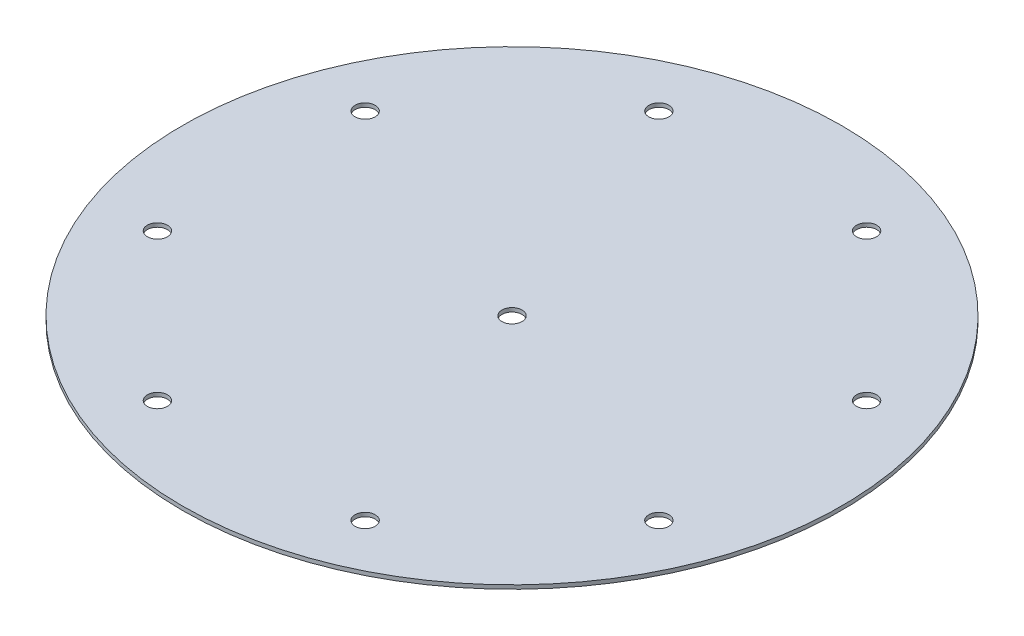
SolidWorks part; units mm, degrees
ref_plane "Front Plane" through (0, 0, 0) normal (0, 0, 1) x (1, 0, 0)
ref_plane "Top Plane" through (0, 0, 0) normal (0, 1, 0) x (1, 0, 0)
ref_plane "Right Plane" through (0, 0, 0) normal (1, 0, 0) x (0, 0, -1)
sketch "Sketch2" plane through (0, 0, 0) normal (1, 0, 0) x (0, 0, -1)
  line L0 (0, 0) -> (-84.9998, 0)
  line L1 (-84.9998, 0) -> (-84.9998, 1)
  line L2 (-84.9998, 1) -> (0, 1)
  line L5 (0, 1) -> (0, 0)
  dimension "D1" = 84.9998
  dimension "D2" = 1
ref_axis "Axis1" through (0, -0.75, 0) along (0, 1, 0)
revolve "Revolve1" add sketch "Sketch2" angle 360 about axis through (0, -0.75, 0) along (0, 1, 0)
hole_wizard "#6 (0.204) Diameter Hole1" positions "Sketch6" profile "Sketch7" hole size "#6" standard "ANSI Inch" end condition through all
sketch "Sketch6" plane through (0, 1, 0) normal (0, 1, 0) x (1, 0, 0)
  line L0 (0, 0) -> (-53.438, 129.0108) construction
  line L2 (0, 0) -> (0, 109.0908) construction
  point P0 (-26.7878, 64.6716)
  dimension "D1" = 22.5
  dimension "D2" = 70
sketch "Sketch7" plane through (-26.7878, 1, -64.6716) normal (1, 0, 0) x (0, 0, 1)
  line L0 (0, 0) -> (0, 1)
  line L1 (0, 1) -> (2.5908, 1)
  line L2 (2.5908, 1) -> (2.5908, 0)
  line L5 (2.5908, 0) -> (0, 0)
  line L11 (0, -6.35) -> (0, 107.95) construction
  dimension "Thru Hole Dia." = 5.1816
  dimension "Thru Hole Depth" = 1
pattern_circular "CirPattern3" count 8 over 360 about axis through (0, -0.75, 0) along (0, 1, 0) of "#6 (0.204) Diameter Hole1"
hole_wizard "#6 (0.204) Diameter Hole2" positions "Sketch8" profile "Sketch9" hole size "#6" standard "ANSI Inch" end condition through all
sketch "Sketch8" plane through (0, 1, 0) normal (0, 1, 0) x (1, 0, 0)
  line L0 (0, 0) -> (106.3094, -1.7118) construction
  point P7 (0, 0)
sketch "Sketch9" plane through (0, 1, 0) normal (1, 0, 0) x (0, 0, 1)
  line L0 (0, 0) -> (0, 1)
  line L1 (0, 1) -> (2.5908, 1)
  line L2 (2.5908, 1) -> (2.5908, 0)
  line L5 (2.5908, 0) -> (0, 0)
  line L11 (0, -6.35) -> (0, 107.95) construction
  dimension "Thru Hole Dia." = 5.1816
  dimension "Thru Hole Depth" = 1
